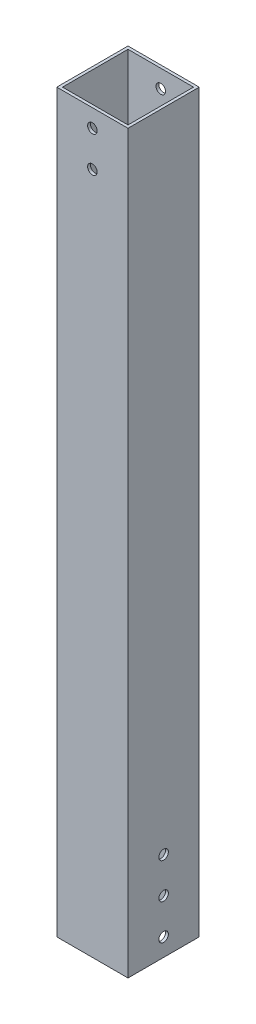
SolidWorks part; units mm, degrees
material "6061 Alloy"
ref_plane "Front Plane" through (0, 0, 0) normal (0, 0, 1) x (1, 0, 0)
ref_plane "Top Plane" through (0, 0, 0) normal (0, 1, 0) x (1, 0, 0)
ref_plane "Right Plane" through (0, 0, 0) normal (1, 0, 0) x (0, 0, -1)
sketch "Sketch1" plane through (0, 0, 0) normal (0, 1, 0) x (1, 0, 0)
  line L1 (19.05, 19.05) -> (-19.05, 19.05)
  line L2 (19.05, 19.05) -> (19.05, -19.05)
  line L3 (19.05, -19.05) -> (-19.05, -19.05)
  line L4 (-19.05, 19.05) -> (-19.05, -19.05)
  line L5 (19.05, 19.05) -> (-19.05, -19.05) construction
  line L6 (19.05, -19.05) -> (-19.05, 19.05) construction
  point P0 (0, 0)
  dimension "D1" = 38.1
extrude "Extrude-Thin1" add sketch "Sketch1" along normal blind 393.7 thin thin type one direction reverse wall 1.524
sketch "Sketch2" plane through (19.05, 0, 0) normal (1, 0, 0) x (0, 0, -1)
  line L0 (-19.05, 0) -> (19.05, 0) construction
  circle A0 centre (0, 9.525) radius 2.54
  circle A1 centre (0, 28.575) radius 2.54
  circle A2 centre (0, 47.625) radius 2.54
  dimension "D1" = 5.08
  dimension "D4" = 19.05
  dimension "D2" = 9.525
  dimension "D3" = 28.575
hole_wizard "#10 Clearance Hole1" positions "Sketch3" profile "Sketch4" hole size "#10" standard "ANSI Inch" end condition through all
sketch "Sketch3" plane through (19.05, 0, 0) normal (1, 0, 0) x (0, 0, -1)
  point P0 (0, 9.525)
  point P3 (0, 28.575)
  point P6 (0, 47.625)
sketch "Sketch4" plane through (19.05, 9.525, 0) normal (0, 1, 0) x (0, 0, -1)
  line L0 (0, 0) -> (0, 38.1)
  line L1 (0, 38.1) -> (2.5527, 38.1)
  line L2 (2.5527, 38.1) -> (2.5527, 0)
  line L5 (2.5527, 0) -> (0, 0)
  line L11 (0, -6.35) -> (0, 107.95) construction
  dimension "Thru Hole Dia." = 5.1054
  dimension "Thru Hole Depth" = 38.1
sketch "Sketch5" plane through (0, 0, 19.05) normal (0, 0, 1) x (1, 0, 0)
  line L0 (-19.05, 393.7) -> (19.05, 393.7) construction
  circle A0 centre (0, 384.175) radius 2.54
  circle A1 centre (0, 365.125) radius 2.54
  dimension "D1" = 5.08
  dimension "D2" = 9.525
  dimension "D3" = 28.575
hole_wizard "#10 Clearance Hole2" positions "Sketch6" profile "Sketch7" hole size "#10" standard "ANSI Inch" end condition through all
sketch "Sketch6" plane through (0, 0, 19.05) normal (0, 0, 1) x (1, 0, 0)
  point P0 (0, 365.125)
  point P3 (0, 384.175)
sketch "Sketch7" plane through (0, 365.125, 19.05) normal (1, 0, 0) x (0, -1, 0)
  line L0 (0, 0) -> (0, 38.1)
  line L1 (0, 38.1) -> (2.5527, 38.1)
  line L2 (2.5527, 38.1) -> (2.5527, 0)
  line L5 (2.5527, 0) -> (0, 0)
  line L11 (0, -6.35) -> (0, 107.95) construction
  dimension "Thru Hole Dia." = 5.1054
  dimension "Thru Hole Depth" = 38.1
